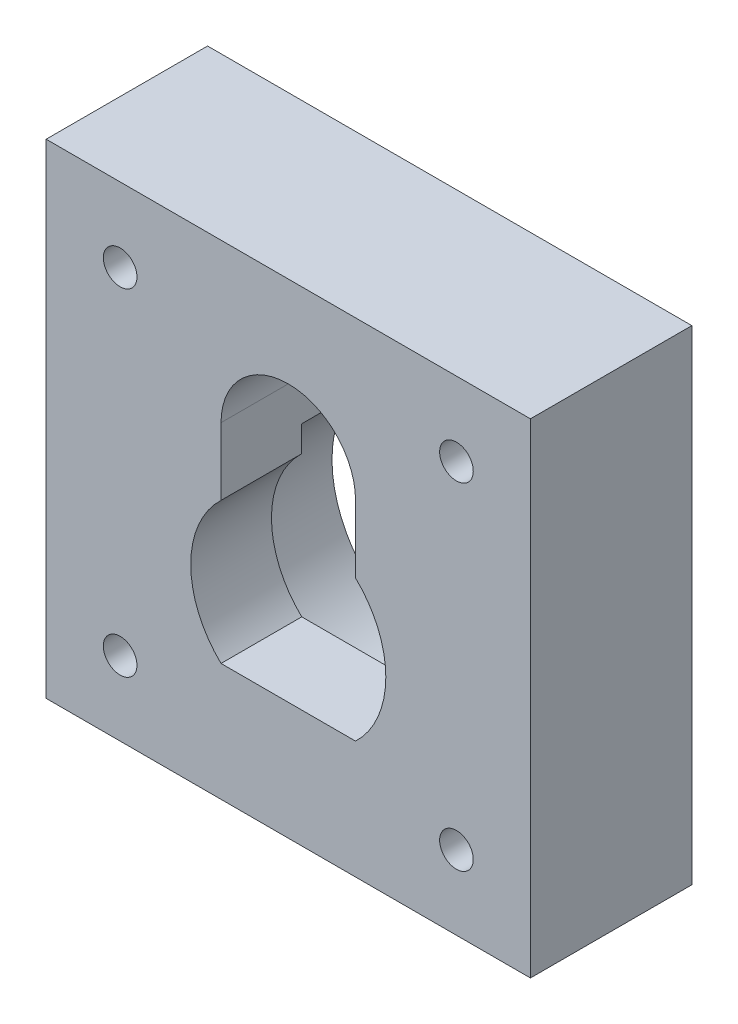
SolidWorks part; units mm, degrees
ref_plane "Front Plane" through (0, 0, 0) normal (0, 0, 1) x (1, 0, 0)
ref_plane "Top Plane" through (0, 0, 0) normal (0, 1, 0) x (1, 0, 0)
ref_plane "Right Plane" through (0, 0, 0) normal (1, 0, 0) x (0, 0, -1)
sketch "Sketch1" plane through (0, 0, 0) normal (0, 0, 1) x (1, 0, 0)
  line L1 (18, -18) -> (-18, -18)
  line L2 (18, -18) -> (18, 18)
  line L3 (18, 18) -> (-18, 18)
  line L4 (-18, -18) -> (-18, 18)
  line L5 (18, -18) -> (-18, 18) construction
  line L6 (18, 18) -> (-18, -18) construction
  point P0 (0, 0)
  dimension "D1" = 36
  dimension "D2" = 36
extrude "Boss-Extrude1" add sketch "Sketch1" along normal blind 12
sketch "Sketch2" plane through (0, 0, 0) normal (0, 0, -1) x (-1, 0, 0)
  line L1 (18, -18) -> (-18, -18) construction
  line L3 (18, 18) -> (18, -18) construction
  circle A0 centre (0, -4) radius 8.75
  dimension "D1" = 17.5
  dimension "D3" = 5.25
  dimension "D4" = 9.25
  dimension "D2" = 4
extrude "Cut-Extrude1" cut sketch "Sketch2" against normal blind 6
sketch "Sketch3" plane through (0, 0, 6) normal (0, 0, -1) x (-1, 0, 0)
  line L0 (-5, 1.25) -> (5, 1.25)
  line L1 (-5, -9.25) -> (5, -9.25)
  line L2 (-7.25, -4) -> (7.25, -4) construction
  arc A0 (-5, 1.25) -> (-5, -9.25) centre (0, -4) ccw
  circle A1 centre (0, -4) radius 8.75 construction
  arc A2 (5, -9.25) -> (5, 1.25) centre (0, -4) ccw
  dimension "D1" = 14.5
  dimension "D2" = 10.5
extrude "Cut-Extrude2" cut sketch "Sketch3" against normal up to next
sketch "Sketch4" plane through (0, 0, 0) normal (0, 0, -1) x (-1, 0, 0)
  line L0 (5, 1.25) -> (-5, 1.25) construction
  line L1 (-5, 6.25) -> (-5, 1.25)
  line L2 (5, 6.25) -> (5, 1.25)
  line L3 (-5, 1.25) -> (5, 1.25)
  arc A0 (5, 6.25) -> (-5, 6.25) centre (0, 6.25) ccw
  dimension "D1" = 10
extrude "Cut-Extrude3" cut sketch "Sketch4" against normal up to next
hole_wizard "M3x0.5 Tapped Hole1" positions "Sketch8" profile "Sketch6" tap size "M3x0.5" standard "ANSI Metric" end condition through all
sketch "Sketch8" plane through (0, 0, 12) normal (0, 0, 1) x (1, 0, 0)
  line L0 (-12.5, 12.5) -> (12.5, 12.5) construction
  line L1 (12.5, 12.5) -> (12.5, -12.5) construction
  point P0 (-12.5, -12.5)
  point P2 (12.5, -12.5)
  point P4 (12.5, 12.5)
  point P6 (-12.5, 12.5)
  point P13 (0, 12.5)
  point P15 (12.5, 0)
  point P16 (0, 0)
  point P17 (0, 0)
  dimension "D1" = 25
  dimension "D2" = 25
sketch "Sketch6" plane through (-12.5, -12.5, 12) normal (1, 0, 0) x (0, -1, 0)
  line L0 (0, 0) -> (0, 12)
  line L1 (0, 12) -> (1.25, 12)
  line L2 (1.25, 12) -> (1.25, 0)
  line L5 (1.25, 0) -> (0, 0)
  line L11 (0, -6.35) -> (0, 107.95) construction
  dimension "Thru Tap Drill Dia." = 2.5
  dimension "Thru Tap Drill Depth" = 12
